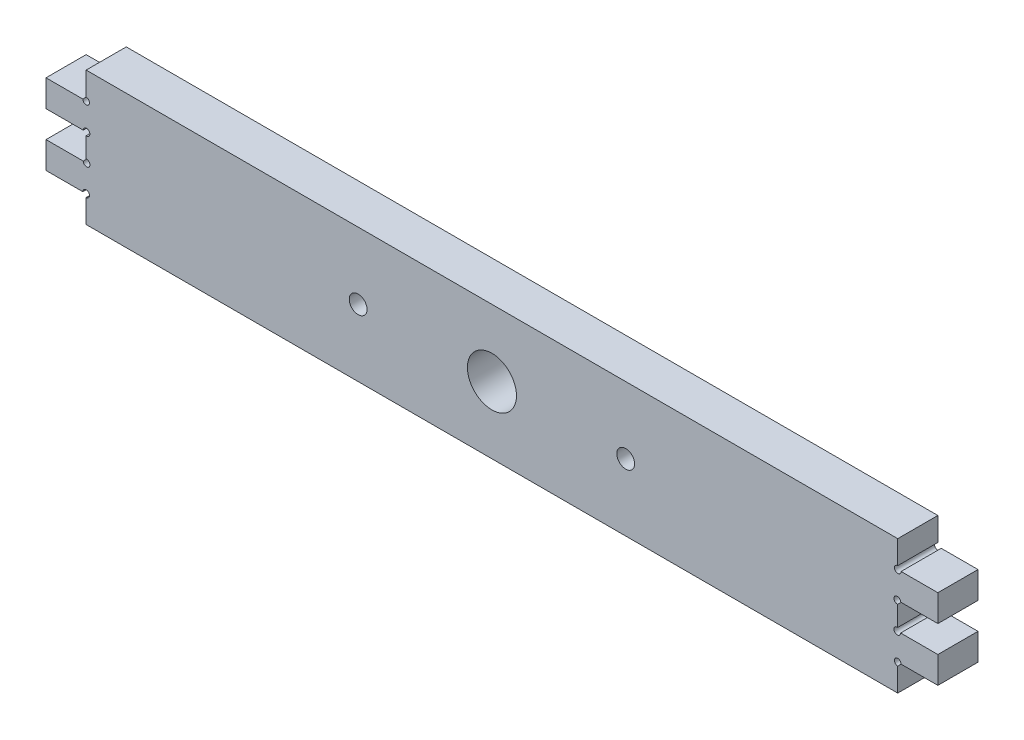
SolidWorks part; units mm, degrees
ref_plane "Front Plane" through (0, 0, 0) normal (0, 0, 1) x (1, 0, 0)
ref_plane "Top Plane" through (0, 0, 0) normal (0, 1, 0) x (1, 0, 0)
ref_plane "Right Plane" through (0, 0, 0) normal (1, 0, 0) x (0, 0, -1)
sketch "Sketch1" plane through (0, 0, 0) normal (0, 0, 1) x (1, 0, 0)
  line L0 (0, -1000) -> (0, 49000) construction
  line L1 (-182, -30) -> (182, -30)
  line L2 (-200, -18) -> (-200, -6)
  line L3 (-182, 30) -> (182, 30)
  line L4 (200, -18) -> (200, -6)
  line L5 (-182, -19.5) -> (-182, -30)
  line L6 (-200, -18) -> (-183.5, -18)
  line L7 (-1000, 0) -> (49000, 0) construction
  line L8 (182, 30) -> (182, 19.5)
  line L9 (200, 18) -> (183.5, 18)
  line L11 (200, -6) -> (183.299, -6)
  line L12 (200, -18) -> (183.5, -18)
  line L13 (182, 4.5) -> (182, -4.5)
  line L14 (200, 6) -> (200, 18)
  line L15 (200, 6) -> (183.299, 6)
  line L16 (182, -19.5) -> (182, -30)
  line L17 (-200, -6) -> (-183.299, -6)
  line L18 (-182, 4.5) -> (-182, -4.5)
  line L19 (-200, 6) -> (-183.299, 6)
  line L20 (-182, 30) -> (-182, 19.5)
  line L21 (-200, 18) -> (-183.5, 18)
  line L22 (-200, 18) -> (-200, 6)
  line L23 (-200, 6) -> (-200, 18)
  line L24 (-200, -6) -> (-200, -18)
  circle A3 centre (0, 0) radius 4
  circle A4 centre (60, 0) radius 4
  circle A5 centre (-60, 0) radius 4
  arc A6 (182, 19.5) -> (183.5, 18) centre (182, 18) ccw
  arc A7 (183.299, 6) -> (182, 4.5) centre (181.7991, 5.9865) ccw
  arc A8 (182, -4.5) -> (183.299, -6) centre (181.7991, -5.9865) ccw
  arc A9 (183.5, -18) -> (182, -19.5) centre (182, -18) ccw
  arc A10 (-183.5, -18) -> (-182, -19.5) centre (-182, -18) cw
  arc A11 (-182, -4.5) -> (-183.299, -6) centre (-181.7991, -5.9865) cw
  arc A12 (-183.299, 6) -> (-182, 4.5) centre (-181.7991, 5.9865) cw
  arc A13 (-182, 19.5) -> (-183.5, 18) centre (-182, 18) cw
  point P0 (0, 0)
  point P1 (-182, 0)
  point P23 (182, 0)
  point P24 (0, -30)
  dimension "D7" = 3
  dimension "D8" = 12
  dimension "D9" = 12
  dimension "D10" = 60
  dimension "D11" = 16.5
  dimension "D4" = 8
  dimension "D13" = 364
  dimension "D14" = 60
  dimension "D15" = 18
  dimension "D2" = 12
  dimension "D3" = 18
  dimension "D6" = 400
  dimension "D12" = 18
  dimension "D5" = 12
extrude "Boss-Extrude1" add sketch "Sketch1" along normal blind 18 contours L21 L22 L19 L18 L17 L2 L6 L5 L1 L16 L12 L4 L11 L13 L14 L9 L8 L3 L20 A5 region at (-177.9553, -24.75, 0)
sketch "Sketch2" plane through (0, 0, 18) normal (0, 0, 1) x (1, 0, 0)
  line L0 (-1000, 0) -> (49000, 0) construction
  line L1 (0, -1000) -> (0, 49000) construction
  circle A0 centre (0, 0) radius 11
  dimension "D1" = 22
extrude "Cut-Extrude1" cut sketch "Sketch2" against normal up to next
